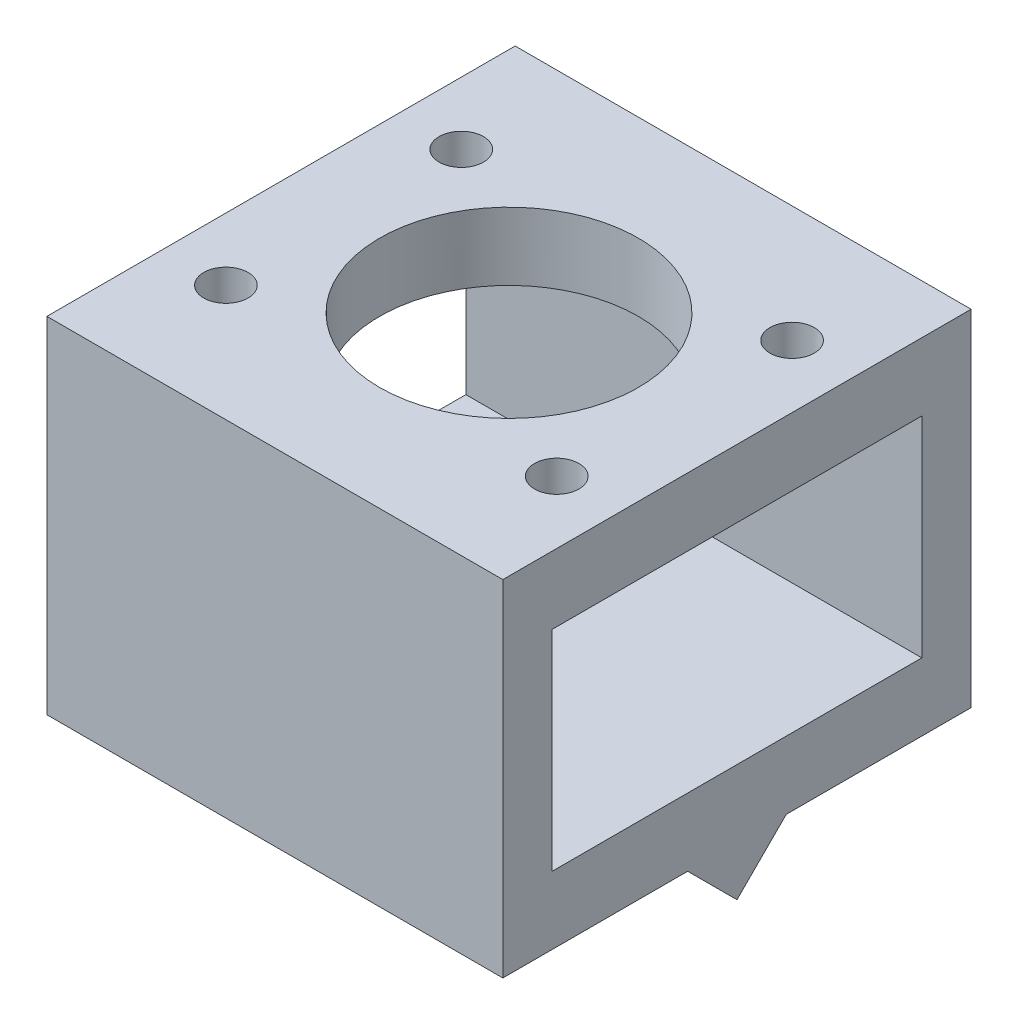
SolidWorks part; units mm, degrees
ref_plane "Front Plane" through (0, 0, 0) normal (0, 0, 1) x (1, 0, 0)
ref_plane "Top Plane" through (0, 0, 0) normal (0, 1, 0) x (1, 0, 0)
ref_plane "Right Plane" through (0, 0, 0) normal (1, 0, 0) x (0, 0, -1)
sketch "Sketch2" plane through (0, 0, 0) normal (1, 0, 0) x (0, 0, -1)
  line L0 (0, -8.5) -> (0, -24.413) construction
  line L1 (19, -14) -> (4, -14)
  line L2 (19, -14) -> (19, 14)
  line L3 (19, 14) -> (-19, 14)
  line L4 (-19, -14) -> (-19, 14)
  line L5 (19, -14) -> (-19, 14) construction
  line L6 (19, 14) -> (-19, -14) construction
  line L7 (-15, -8.5) -> (15, -8.5)
  line L8 (-15, -8.5) -> (-15, 8.5)
  line L9 (-15, 8.5) -> (15, 8.5)
  line L10 (15, -8.5) -> (15, 8.5)
  line L11 (-15, -8.5) -> (15, 8.5) construction
  line L12 (-15, 8.5) -> (15, -8.5) construction
  line L13 (0, -18) -> (-4, -14)
  line L14 (0, -18) -> (4, -14)
  line L15 (-4, -14) -> (-19, -14)
  point P0 (0, 0)
  point P5 (0, 0)
  dimension "D1" = 28
  dimension "D2" = 38
  dimension "D3" = 17
  dimension "D4" = 30
  dimension "D5" = 5.6569
  dimension "D6" = 45
extrude "Boss-Extrude1" add sketch "Sketch2" along normal blind 37
sketch "Sketch3" plane through (0, 14, 0) normal (0, 1, 0) x (1, 0, 0)
  line L0 (0, 0) -> (37, 0) construction
  line L1 (37, 19) -> (37, -19) construction
  line L2 (0, 19) -> (0, -19) construction
  line L3 (37, -19) -> (0, -19) construction
  line L4 (18.5, 19) -> (18.5, -19) construction
  circle A0 centre (5.0766, -9.55) radius 1.8
  circle A1 centre (5.0766, 9.55) radius 1.8
  circle A2 centre (31.9234, -9.55) radius 1.8
  circle A3 centre (31.9234, 9.55) radius 1.8
  circle A4 centre (18.5, 0) radius 10.5
  point P16 (18.5, 0)
  dimension "D1" = 3.6
  dimension "D4" = 21
  dimension "D2" = 5.0766
  dimension "D3" = 9.45
extrude "Cut-Extrude1" cut sketch "Sketch3" against normal up to next
